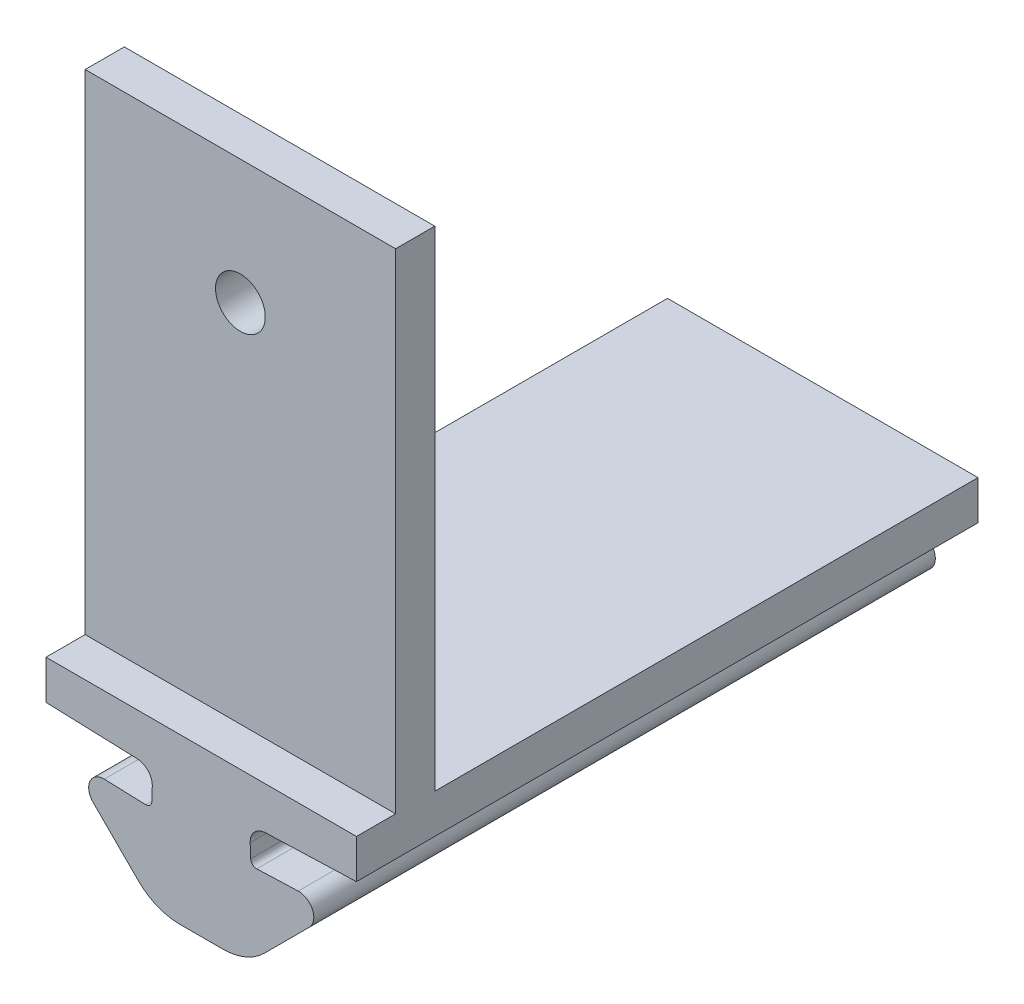
SolidWorks part; units mm, degrees
ref_plane "Front Plane" through (0, 0, 0) normal (0, 0, 1) x (1, 0, 0)
ref_plane "Top Plane" through (0, 0, 0) normal (0, 1, 0) x (1, 0, 0)
ref_plane "Right Plane" through (0, 0, 0) normal (1, 0, 0) x (0, 0, -1)
sketch "Sketch2" plane through (0, 0, 0) normal (0, 0, 1) x (1, 0, 0)
  line L1 (-50.3756, 45.6099) -> (-50.3512, 46.3094)
  line L2 (-50.6859, 45.3205) -> (-52.8037, 45.3945)
  line L6 (-55.7809, 47.2995) -> (-51.1228, 47.1369)
  line L7 (-51.0743, 41.7794) -> (-53.3751, 44.0803)
  line L8 (-47.8507, 40.9008) -> (-48.9529, 40.9008)
  line L9 (-47.8507, 40.9008) -> (-47.8507, 47.2995)
  line L10 (-47.8507, 47.2995) -> (-55.7809, 47.2995)
  arc A0 (-50.6859, 45.3205) -> (-50.3756, 45.6099) centre (-50.6754, 45.6203) ccw
  arc A7 (-50.3512, 46.3094) -> (-51.1228, 47.1369) centre (-51.1507, 46.3374) ccw
  arc A8 (-52.8037, 45.3945) -> (-53.3751, 44.0803) centre (-52.8306, 44.6248) ccw
  arc A9 (-51.0743, 41.7794) -> (-48.9529, 40.9008) centre (-48.9529, 43.9008) ccw
extrude "Boss-Extrude1" add sketch "Sketch2" along normal blind 31.75
ref_plane "Plane2" through (0, 0, 0) normal (0.7071, -0.7071, 0) x (-0.7071, -0.7071, 0)
ref_plane "Plane3" through (-42.746, 42.746, 0) normal (0.7071, -0.7071, 0) x (-0.7071, -0.7071, 0)
mirror "Mirror2" about plane through (-47.8507, 40.9008, 31.75) normal (-1, 0, 0) of "Boss-Extrude1"
ref_plane "Plane7" through (0, 47.2995, 0) normal (0, 1, 0) x (1, 0, 0)
sketch "Sketch19" plane through (0, 47.2995, 0) normal (0, 1, 0) x (1, 0, 0)
  line L0 (-55.7809, -31.75) -> (-55.7809, 0) construction
  line L1 (-55.7809, 0) -> (-39.9205, 0)
  line L2 (-55.7809, 0) -> (-55.7809, -31.75)
  line L3 (-55.7809, -31.75) -> (-39.9205, -31.75)
  line L4 (-39.9205, 0) -> (-39.9205, -31.75)
  line L5 (-39.9205, -31.75) -> (-39.9205, 0) construction
  line L6 (-39.9205, 0) -> (-55.7809, 0) construction
  dimension "D1" = 0
  dimension "D2" = 31.75
extrude "Boss-Extrude7" add sketch "Sketch19" along normal blind 2
sketch "Sketch23" plane through (0, 49.2995, 0) normal (0, 1, 0) x (1, 0, 0)
  line L0 (-55.7809, 0) -> (-55.7809, -31.75) construction
  line L1 (-55.7809, -27.75) -> (-39.9205, -27.75)
  line L2 (-55.7809, -27.75) -> (-55.7809, -29.75)
  line L3 (-55.7809, -29.75) -> (-39.9205, -29.75)
  line L4 (-39.9205, -27.75) -> (-39.9205, -29.75)
  line L5 (-39.9205, -31.75) -> (-39.9205, 0) construction
  line L6 (-39.9205, 0) -> (-55.7809, 0) construction
  dimension "D1" = 2
  dimension "D2" = 0
  dimension "D3" = 0
  dimension "D4" = 29.75
extrude "Boss-Extrude8" add sketch "Sketch23" along normal blind 25
ref_plane "Plane8" through (-39.9205, 49.2995, 27.75) normal (0, -1, 0) x (-1, 0, 0)
sketch "Sketch24" plane through (0, 0, 27.75) normal (0, 0, -1) x (-1, 0, 0)
  line L0 (39.9205, 74.2995) -> (55.7809, 74.2995) construction
  line L5 (47.8507, 74.2995) -> (47.8507, 61.5995) construction
  circle A1 centre (47.8507, 67.9495) radius 1.27
  dimension "D1" = 6.35
  dimension "D4" = 2.54
extrude "Cut-Extrude1" cut sketch "Sketch24" against normal blind 2.54
